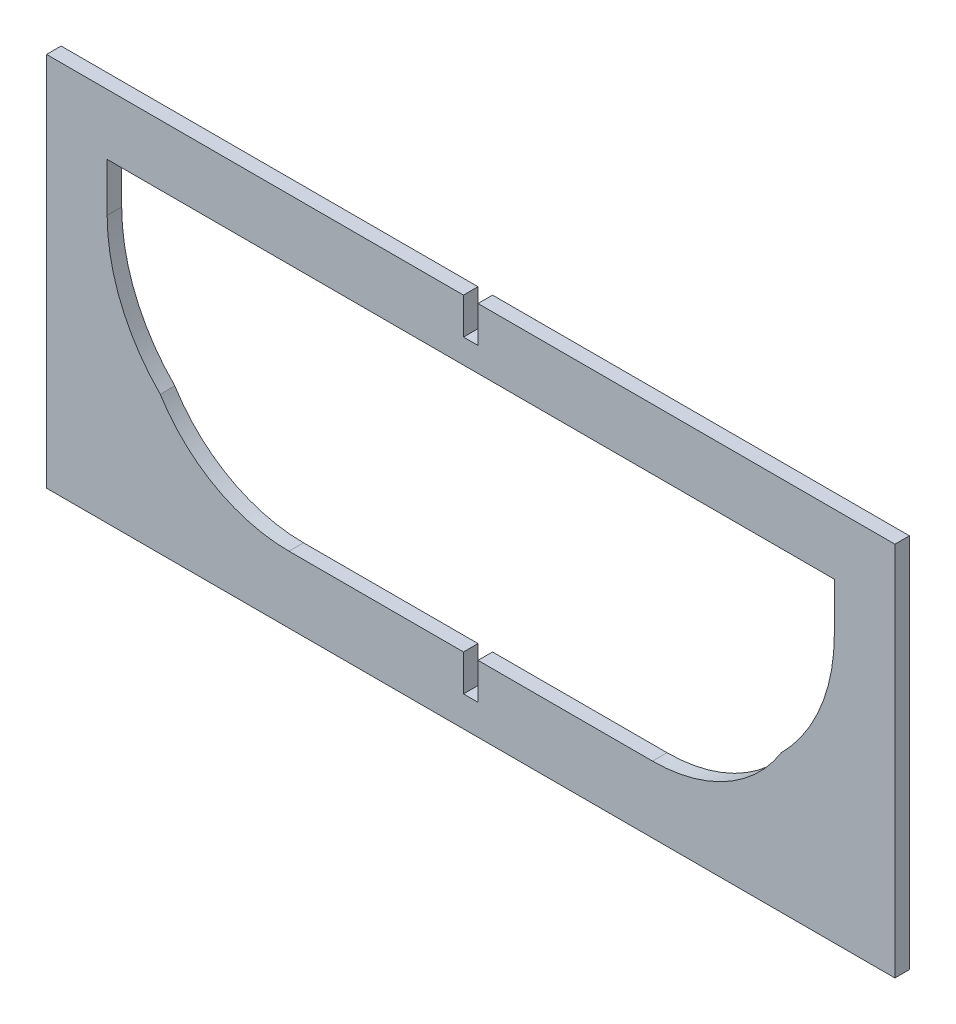
SolidWorks part; units mm, degrees
ref_plane "Front" through (0, 0, 0) normal (0, 0, 1) x (1, 0, 0)
ref_plane "Top" through (0, 0, 0) normal (0, 1, 0) x (1, 0, 0)
ref_plane "Right" through (0, 0, 0) normal (1, 0, 0) x (0, 0, -1)
sketch "Sketch1" plane through (0, 0, 0) normal (0, 0, 1) x (1, 0, 0)
  line L0 (-175, 130) -> (-200, 130)
  line L1 (0, 0) -> (-200, 0)
  line L2 (0, 0) -> (0, 130)
  line L3 (0, 130) -> (-25, 130)
  line L4 (-200, 0) -> (-200, 130)
  line L5 (-100, 90) -> (-100, 0) construction
  line L6 (-175, 110) -> (-175, 130)
  line L7 (-25, 110) -> (-25, 130)
  arc A0 (-153.0972, 57.0313) -> (-46.9028, 57.0312) centre (-100, 90) ccw
  arc A1 (-175, 110) -> (-153.0972, 57.0313) centre (-100, 110) ccw
  arc A2 (-46.9028, 57.0312) -> (-25, 110) centre (-100, 110) ccw
  point P6 (-175, 175)
  dimension "D3" = 62.5
  dimension "D4" = 75
  dimension "D1" = 200
  dimension "D2" = 130
  dimension "D5" = 20
  dimension "D6" = 90
extrude "Boss-Extrude1" add sketch "Sketch1" along normal blind 6
sketch "Sketch2" plane through (0, 0, 6) normal (0, 0, 1) x (1, 0, 0)
  line L0 (0, 0) -> (0, 130) construction
  line L1 (-200, 130) -> (0, 130)
  line L2 (-200, 130) -> (-200, 155)
  line L3 (-200, 155) -> (0, 155)
  line L4 (0, 130) -> (0, 155)
  dimension "D1" = 25
extrude "Boss-Extrude2" add sketch "Sketch2" against normal blind 6
sketch "Sketch3" plane through (0, 0, 6) normal (0, 0, 1) x (1, 0, 0)
  line L0 (-200, 155) -> (-200, 0) construction
  line L1 (-100, 27.5) -> (-200, 27.5)
  line L2 (-100, 27.5) -> (-100, 130)
  line L3 (-100, 130) -> (-200, 130)
  line L4 (-200, 27.5) -> (-200, 130)
  line L5 (-175, 130) -> (-25, 130) construction
  arc A0 (-153.0972, 57.0313) -> (-46.9028, 57.0312) centre (-100, 90) ccw construction
extrude "Cut-Extrude1" cut sketch "Sketch3" against normal blind 6
sketch "Sketch4" plane through (0, 0, 6) normal (0, 0, 1) x (1, 0, 0)
  line L0 (-250, 110) -> (-100, 110) construction
  line L1 (-100, 90) -> (-250, 90) construction
  line L2 (-250, 90) -> (-250, 110) construction
  line L3 (-25, 130) -> (0, 130) construction
  line L4 (-200, 27.5) -> (-250, 27.5)
  line L5 (-200, 27.5) -> (-200, 0)
  line L6 (-200, 0) -> (-350, 0)
  line L7 (-350, 27.5) -> (-350, 0)
  line L9 (-350, 27.5) -> (-350, 155)
  line L10 (-350, 155) -> (-325, 155)
  line L11 (-325, 110) -> (-325, 130)
  line L12 (-200, 130) -> (-325, 130)
  line L13 (-200, 130) -> (-200, 155)
  line L14 (-200, 155) -> (-325, 155)
  line L16 (0, 0) -> (0, 155) construction
  line L17 (-325, 130) -> (-350, 130) construction
  line L18 (-200, 0) -> (0, 0) construction
  arc A0 (-325, 110) -> (-303.0972, 57.0312) centre (-250, 110) ccw
  circle A1 centre (-100, 90) radius 62.5 construction
  circle A2 centre (-100, 110) radius 75 construction
  arc A3 (-46.9028, 57.0312) -> (-25, 110) centre (-100, 110) ccw construction
  arc A4 (-100, 27.5) -> (-46.9028, 57.0312) centre (-100, 90) ccw construction
  arc A5 (-303.0972, 57.0312) -> (-250, 27.5) centre (-250, 90) ccw
  dimension "D1" = 150
  dimension "D2" = 125
  dimension "D4" = 125
  dimension "D3" = 150
extrude "Boss-Extrude3" add sketch "Sketch4" against normal blind 6
sketch "Sketch5" plane through (0, 0, 6) normal (0, 0, 1) x (1, 0, 0)
  line L0 (0, 155) -> (-350, 155) construction
  line L1 (-178, 155) -> (-172, 155)
  line L2 (-178, 155) -> (-178, 140)
  line L3 (-178, 140) -> (-172, 140)
  line L4 (-172, 155) -> (-172, 140)
  line L5 (-250, 27.5) -> (-100, 27.5) construction
  line L6 (-178, 27.5) -> (-172, 27.5)
  line L7 (-178, 27.5) -> (-178, 12.5)
  line L8 (-178, 12.5) -> (-172, 12.5)
  line L9 (-172, 27.5) -> (-172, 12.5)
  point P12 (-175, 155)
  point P13 (-175, 155)
  dimension "D1" = 6
  dimension "D2" = 15
extrude "Cut-Extrude2" cut sketch "Sketch5" against normal blind 6
